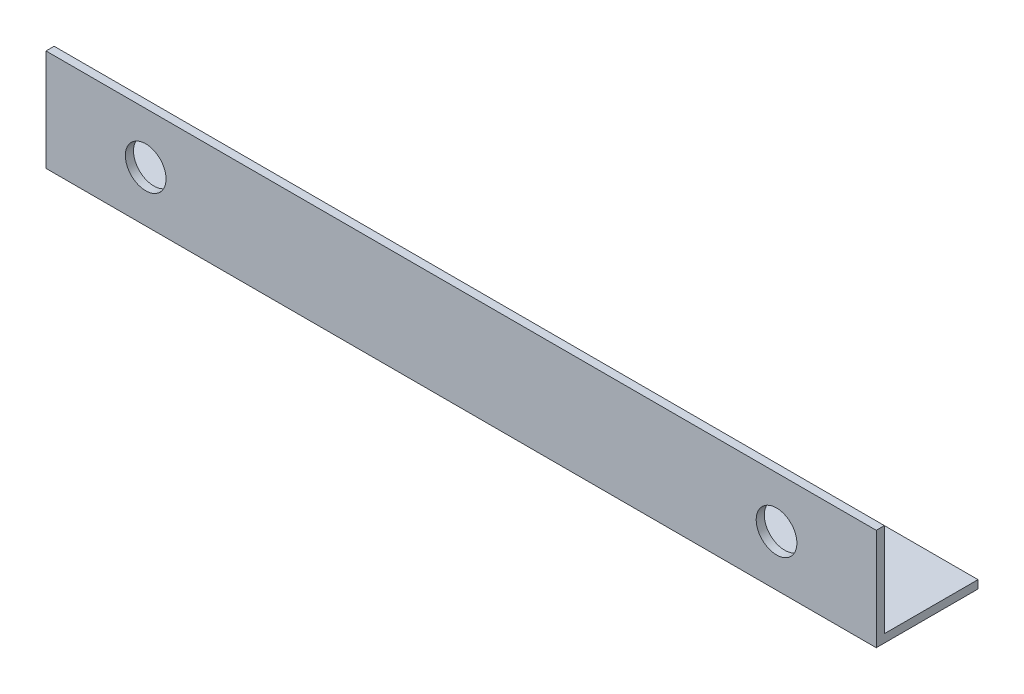
SolidWorks part; units mm, degrees
ref_plane "Спереди" through (0, 0, 0) normal (0, 0, 1) x (1, 0, 0)
ref_plane "Сверху" through (0, 0, 0) normal (0, 1, 0) x (1, 0, 0)
ref_plane "Справа" through (0, 0, 0) normal (1, 0, 0) x (0, 0, -1)
sketch "Эскиз1" plane through (0, 0, 0) normal (1, 0, 0) x (0, 0, -1)
  line L0 (0, 25) -> (0, 0)
  line L1 (0, 0) -> (25, 0)
extrude "Вытянуть-Тонкостенный1" add sketch "Эскиз1" along normal blind 204 thin thin type one direction reverse wall 2
sketch "Эскиз2" plane through (0, 0, 0) normal (0, 0, 1) x (1, 0, 0)
  line L0 (102, 0) -> (102, -9.5468) construction
  line L1 (204, 0) -> (0, 0) construction
  circle A0 centre (24.5, 12.5) radius 5
  circle A1 centre (179.5, 12.5) radius 5
  dimension "D1" = 77.5
extrude "Вырез-Вытянуть1" cut sketch "Эскиз2" against normal through all
